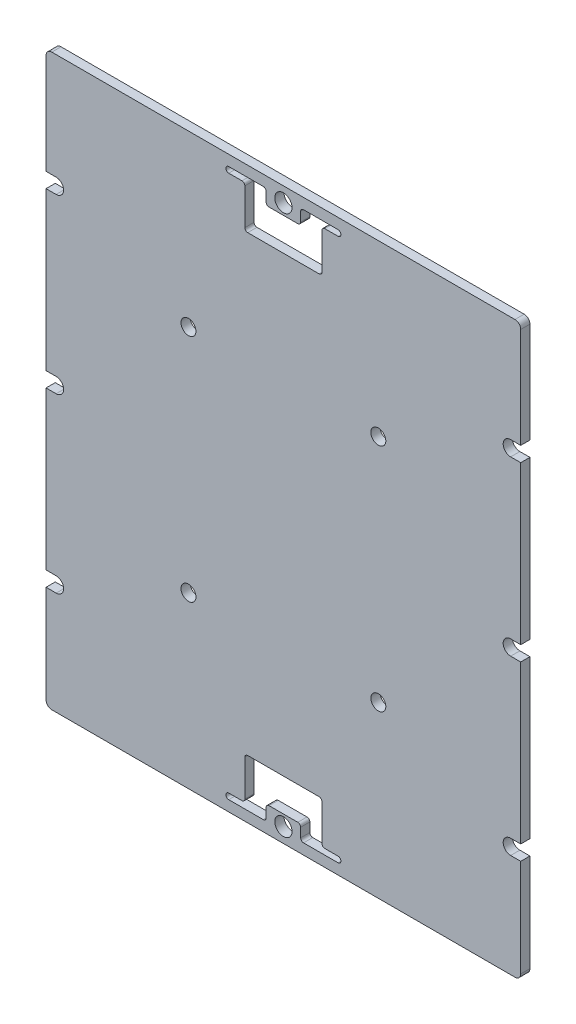
SolidWorks part; units mm, degrees
material "FR4_stuffedProtoboard"
ref_plane "Front Plane" through (0, 0, 0) normal (0, 0, 1) x (1, 0, 0)
ref_plane "Top Plane" through (0, 0, 0) normal (0, 1, 0) x (1, 0, 0)
ref_plane "Right Plane" through (0, 0, 0) normal (1, 0, 0) x (0, 0, -1)
sketch "Sketch2" plane through (0, 0, 0) normal (0, 0, 1) x (1, 0, 0)
  line L0 (39.5, 49.75) -> (-39.5, 49.75) construction
  line L1 (-41.5, 49.75) -> (41.5, 49.75) construction
  line L2 (-41.5, 49.75) -> (-41.5, -49.75) construction
  line L3 (-41.5, -49.75) -> (41.5, -49.75) construction
  line L4 (41.5, 49.75) -> (41.5, -49.75) construction
  line L5 (-41.5, 49.75) -> (41.5, -49.75) construction
  line L6 (-41.5, -49.75) -> (41.5, 49.75) construction
  line L7 (41.5, 51.75) -> (41.5, 40.35) construction
  line L8 (-41.5, 49.75) -> (41.5, 49.75) construction
  line L9 (41.5, 49.75) -> (41.5, -49.75) construction
  line L10 (-41.5, -49.75) -> (41.5, -49.75) construction
  line L11 (-41.5, 49.75) -> (-41.5, -49.75) construction
  line L12 (-37, -31.85) -> (37, -31.85) construction
  line L13 (-37, -30.25) -> (37, -30.25) construction
  line L14 (-37, -21.85) -> (37, -21.85) construction
  line L15 (-37, -20.25) -> (37, -20.25) construction
  line L16 (-37, -11.85) -> (37, -11.85) construction
  line L17 (-37, -10.25) -> (37, -10.25) construction
  line L18 (-37, -1.85) -> (37, -1.85) construction
  line L19 (-37, -0.25) -> (37, -0.25) construction
  line L20 (-37, 8.15) -> (37, 8.15) construction
  line L21 (-37, 9.75) -> (37, 9.75) construction
  line L22 (-37, 18.15) -> (37, 18.15) construction
  line L23 (-37, 19.75) -> (37, 19.75) construction
  line L24 (-37, 28.15) -> (37, 28.15) construction
  line L25 (-37, 29.75) -> (37, 29.75) construction
  line L26 (-37, 38.15) -> (37, 38.15) construction
  line L27 (-37, 39.75) -> (37, 39.75) construction
  line L28 (-37, -31.85) -> (37, -31.85) construction
  line L29 (-37, -30.25) -> (37, -30.25) construction
  line L30 (-37, -21.85) -> (37, -21.85) construction
  line L31 (-37, -20.25) -> (37, -20.25) construction
  line L32 (-37, -11.85) -> (37, -11.85) construction
  line L33 (-37, -10.25) -> (37, -10.25) construction
  line L34 (-37, -1.85) -> (37, -1.85) construction
  line L35 (-37, -0.25) -> (37, -0.25) construction
  line L36 (-37, 8.15) -> (37, 8.15) construction
  line L37 (-37, 9.75) -> (37, 9.75) construction
  line L38 (-37, 18.15) -> (37, 18.15) construction
  line L39 (-37, 19.75) -> (37, 19.75) construction
  line L40 (-37, 28.15) -> (37, 28.15) construction
  line L41 (-37, 29.75) -> (37, 29.75) construction
  line L42 (-37, 38.15) -> (37, 38.15) construction
  line L43 (-37, 39.75) -> (37, 39.75) construction
  line L44 (-37, -40.25) -> (37, -40.25) construction
  line L45 (-37, -41.85) -> (37, -41.85) construction
  line L46 (-41.5, 51.75) -> (-41.5, 40.35) construction
  line L47 (39.5, -49.75) -> (-39.5, -49.75) construction
  line L48 (41.5, -31.9) -> (41.5, -51.75) construction
  line L49 (-41.25, 49.5) -> (41.25, 49.5)
  line L50 (41.25, 49.5) -> (41.25, -49.5)
  line L51 (-41.25, -49.5) -> (41.25, -49.5)
  line L52 (-41.25, 49.5) -> (-41.25, -49.5)
  circle A0 centre (0, 46.95) radius 1.5 construction
  circle A1 centre (0, 46.95) radius 0.8 construction
  circle A2 centre (0, 46.95) radius 1.5 construction
  circle A3 centre (0, 46.95) radius 0.8
  circle A4 centre (-39.5, -30.25) radius 0.8 construction
  circle A5 centre (-39.5, -0.25) radius 0.8 construction
  circle A6 centre (-39.5, 29.75) radius 0.8 construction
  circle A7 centre (-39.5, -30.25) radius 0.8
  circle A8 centre (-39.5, -0.25) radius 0.8
  circle A9 centre (-39.5, 29.75) radius 0.8
  circle A10 centre (39.5, -30.25) radius 0.8 construction
  circle A11 centre (39.5, -0.25) radius 0.8 construction
  circle A12 centre (39.5, 29.75) radius 0.8 construction
  circle A13 centre (39.5, -30.25) radius 0.8
  circle A14 centre (39.5, -0.25) radius 0.8
  circle A15 centre (39.5, 29.75) radius 0.8
  circle A16 centre (0, -46.95) radius 0.8 construction
  circle A17 centre (0, -46.95) radius 0.8
  circle A18 centre (0, -46.95) radius 1.5 construction
  circle A19 centre (0, -46.95) radius 1.5
  circle A20 centre (-16.5, 20) radius 1.75 construction
  circle A21 centre (-16.5, 20) radius 0.8 construction
  circle A22 centre (-16.5, 20) radius 1.75 construction
  circle A23 centre (-16.5, 20) radius 0.8
  circle A24 centre (16.5, 20) radius 1.75 construction
  circle A25 centre (16.5, 20) radius 0.8 construction
  circle A26 centre (16.5, 20) radius 1.75 construction
  circle A27 centre (16.5, 20) radius 0.8
  circle A28 centre (16.5, -20) radius 1.75 construction
  circle A29 centre (-16.5, -20) radius 1.75 construction
  circle A30 centre (16.5, -20) radius 1.75 construction
  circle A31 centre (-16.5, -20) radius 1.75 construction
  circle A32 centre (-16.5, -20) radius 0.8 construction
  circle A33 centre (-16.5, -20) radius 0.8
  circle A34 centre (16.5, -20) radius 0.8 construction
  circle A35 centre (16.5, -20) radius 0.8
  point P0 (0, 0)
  point P74 (0, -40.25)
  point P75 (0, -31.85)
  point P76 (0, -41.85)
  dimension "D2" = 10
  dimension "D3" = 1.6
  dimension "D1" = 0.25
extrude "pcb extrude" add sketch "Sketch2" along normal mid plane 1.6 contours L4 L1 L2 L3 A2 | A2 A3 | L2 L1 L4 L3 region at (0, 0.0296, 0)
sketch "connector locations" plane through (0, 0, 0.8) normal (0, 0, 1) x (1, 0, 0)
  line L0 (34.5, 45.75) -> (4.5, 45.75) construction
  line L1 (-2.5, 44.75) -> (2.5, 44.75) construction
  line L2 (-4.5, 45.75) -> (-34.5, 45.75) construction
  line L3 (34.5, 45.75) -> (4.5, 45.75)
  line L4 (-2.5, 44.75) -> (2.5, 44.75)
  line L5 (-4.5, 45.75) -> (-34.5, 45.75)
  line L6 (-37, 43.25) -> (-37, -43.25) construction
  line L7 (-37, 43.25) -> (-37, -43.25)
  line L8 (37, -43.25) -> (37, 43.25) construction
  line L9 (37, -43.25) -> (37, 43.25)
  line L10 (4.5, -45.75) -> (34.5, -45.75) construction
  line L11 (4.5, -45.75) -> (34.5, -45.75)
  line L12 (-34.5, -45.75) -> (-4.5, -45.75) construction
  line L13 (-2.5, -44.75) -> (2.5, -44.75) construction
  line L14 (-34.5, -45.75) -> (-4.5, -45.75)
  line L15 (-2.5, -44.75) -> (2.5, -44.75)
  line L16 (-37, 39.75) -> (37, 39.75) construction
  line L17 (-33.9182, 41.909) -> (-9.2802, 41.909)
  line L18 (-33.9182, 41.909) -> (-33.9182, 43.306)
  line L19 (-33.9182, 43.306) -> (-9.2802, 43.306)
  line L20 (-9.2802, 41.909) -> (-9.2802, 43.306)
  line L21 (-33.9182, 41.909) -> (-9.2802, 43.306) construction
  line L22 (-33.9182, 43.306) -> (-9.2802, 41.909) construction
  line L23 (-33.9182, 33.306) -> (-22.0818, 33.306)
  line L24 (-33.9182, 33.306) -> (-33.9182, 31.909)
  line L25 (-33.9182, 31.909) -> (-22.0818, 31.909)
  line L26 (-22.0818, 33.306) -> (-22.0818, 31.909)
  line L27 (-33.9182, 33.306) -> (-22.0818, 31.909) construction
  line L28 (-33.9182, 31.909) -> (-22.0818, 33.306) construction
  line L29 (-12.319, 33.306) -> (12.319, 33.306)
  line L30 (-12.319, 33.306) -> (-12.319, 31.909)
  line L31 (-12.319, 31.909) -> (12.319, 31.909)
  line L32 (12.319, 33.306) -> (12.319, 31.909)
  line L33 (-12.319, 33.306) -> (12.319, 31.909) construction
  line L34 (-12.319, 31.909) -> (12.319, 33.306) construction
  line L35 (-33.9182, 23.306) -> (-22.0818, 23.306)
  line L36 (-33.9182, 23.306) -> (-33.9182, 21.909)
  line L37 (-33.9182, 21.909) -> (-22.0818, 21.909)
  line L38 (-33.9182, 23.306) -> (-22.0818, 21.909) construction
  line L39 (-33.9182, 21.909) -> (-22.0818, 23.306) construction
  line L40 (-22.0818, 23.306) -> (-22.0818, 21.909)
  line L41 (-12.319, 23.306) -> (-12.319, 21.909)
  line L42 (-12.319, 23.306) -> (12.319, 23.306)
  line L43 (-12.319, 21.909) -> (12.319, 21.909)
  line L44 (-12.319, 23.306) -> (12.319, 21.909) construction
  line L45 (-12.319, 21.909) -> (12.319, 23.306) construction
  line L46 (12.319, 23.306) -> (12.319, 21.909)
  line L47 (-33.9182, 13.306) -> (-22.0818, 13.306)
  line L48 (-33.9182, 13.306) -> (-33.9182, 11.909)
  line L49 (-33.9182, 11.909) -> (-22.0818, 11.909)
  line L50 (-33.9182, 13.306) -> (-22.0818, 11.909) construction
  line L51 (-33.9182, 11.909) -> (-22.0818, 13.306) construction
  line L52 (-22.0818, 13.306) -> (-22.0818, 11.909)
  line L53 (-12.319, 13.306) -> (-12.319, 11.909)
  line L54 (-12.319, 13.306) -> (12.319, 13.306)
  line L55 (-12.319, 11.909) -> (12.319, 11.909)
  line L56 (-12.319, 13.306) -> (12.319, 11.909) construction
  line L57 (-12.319, 11.909) -> (12.319, 13.306) construction
  line L58 (12.319, 13.306) -> (12.319, 11.909)
  line L59 (-33.9182, 3.306) -> (-22.0818, 3.306)
  line L60 (-33.9182, 3.306) -> (-33.9182, 1.909)
  line L61 (-33.9182, 1.909) -> (-22.0818, 1.909)
  line L62 (-33.9182, 3.306) -> (-22.0818, 1.909) construction
  line L63 (-33.9182, 1.909) -> (-22.0818, 3.306) construction
  line L64 (-22.0818, 3.306) -> (-22.0818, 1.909)
  line L65 (-12.319, 3.306) -> (-12.319, 1.909)
  line L66 (-12.319, 3.306) -> (12.319, 3.306)
  line L67 (-12.319, 1.909) -> (12.319, 1.909)
  line L68 (-12.319, 3.306) -> (12.319, 1.909) construction
  line L69 (-12.319, 1.909) -> (12.319, 3.306) construction
  line L70 (12.319, 3.306) -> (12.319, 1.909)
  line L71 (-33.9182, -6.694) -> (-22.0818, -6.694)
  line L72 (-33.9182, -6.694) -> (-33.9182, -8.091)
  line L73 (-33.9182, -8.091) -> (-22.0818, -8.091)
  line L74 (-33.9182, -6.694) -> (-22.0818, -8.091) construction
  line L75 (-33.9182, -8.091) -> (-22.0818, -6.694) construction
  line L76 (-22.0818, -6.694) -> (-22.0818, -8.091)
  line L77 (-12.319, -6.694) -> (-12.319, -8.091)
  line L78 (-12.319, -6.694) -> (12.319, -6.694)
  line L79 (-12.319, -8.091) -> (12.319, -8.091)
  line L80 (-12.319, -6.694) -> (12.319, -8.091) construction
  line L81 (-12.319, -8.091) -> (12.319, -6.694) construction
  line L82 (12.319, -6.694) -> (12.319, -8.091)
  line L83 (-33.9182, -16.694) -> (-22.0818, -16.694)
  line L84 (-33.9182, -16.694) -> (-33.9182, -18.091)
  line L85 (-33.9182, -18.091) -> (-22.0818, -18.091)
  line L86 (-33.9182, -16.694) -> (-22.0818, -18.091) construction
  line L87 (-33.9182, -18.091) -> (-22.0818, -16.694) construction
  line L88 (-22.0818, -16.694) -> (-22.0818, -18.091)
  line L89 (-12.319, -16.694) -> (-12.319, -18.091)
  line L90 (-12.319, -16.694) -> (12.319, -16.694)
  line L91 (-12.319, -18.091) -> (12.319, -18.091)
  line L92 (-12.319, -16.694) -> (12.319, -18.091) construction
  line L93 (-12.319, -18.091) -> (12.319, -16.694) construction
  line L94 (12.319, -16.694) -> (12.319, -18.091)
  line L95 (-33.9182, -26.694) -> (-22.0818, -26.694)
  line L96 (-33.9182, -26.694) -> (-33.9182, -28.091)
  line L97 (-33.9182, -28.091) -> (-22.0818, -28.091)
  line L98 (-33.9182, -26.694) -> (-22.0818, -28.091) construction
  line L99 (-33.9182, -28.091) -> (-22.0818, -26.694) construction
  line L100 (-22.0818, -26.694) -> (-22.0818, -28.091)
  line L101 (-12.319, -26.694) -> (-12.319, -28.091)
  line L102 (-12.319, -26.694) -> (12.319, -26.694)
  line L103 (-12.319, -28.091) -> (12.319, -28.091)
  line L104 (-12.319, -26.694) -> (12.319, -28.091) construction
  line L105 (-12.319, -28.091) -> (12.319, -26.694) construction
  line L106 (12.319, -26.694) -> (12.319, -28.091)
  line L111 (-35.52, -38.1) -> (-10.98, -38.1)
  line L116 (-35.52, -38.1) -> (-35.52, -37.9)
  line L117 (-35.52, -37.9) -> (-10.98, -37.9)
  line L119 (0, 32.6075) -> (0, 22.6075) construction
  line L120 (-37, 29.75) -> (37, 29.75) construction
  line L121 (32.92, 41.02) -> (35.08, 38.84) construction
  line L122 (32.92, 38.84) -> (35.08, 41.02) construction
  line L123 (26.92, 38.84) -> (29.08, 41.02) construction
  line L124 (26.92, 41.02) -> (29.08, 38.84) construction
  line L125 (20.92, 38.84) -> (23.08, 41.02) construction
  line L126 (20.92, 41.02) -> (23.08, 38.84) construction
  line L127 (26.92, 28.84) -> (29.08, 31.02) construction
  line L128 (26.92, 31.02) -> (29.08, 28.84) construction
  line L129 (20.92, 28.84) -> (23.08, 31.02) construction
  line L130 (20.92, 31.02) -> (23.08, 28.84) construction
  line L131 (26.92, 18.84) -> (29.08, 21.02) construction
  line L132 (26.92, 21.02) -> (29.08, 18.84) construction
  line L133 (20.92, 18.84) -> (23.08, 21.02) construction
  line L134 (20.92, 21.02) -> (23.08, 18.84) construction
  line L135 (26.92, 8.84) -> (29.08, 11.02) construction
  line L136 (26.92, 11.02) -> (29.08, 8.84) construction
  line L137 (20.92, 8.84) -> (23.08, 11.02) construction
  line L138 (20.92, 11.02) -> (23.08, 8.84) construction
  line L139 (26.92, -1.16) -> (29.08, 1.02) construction
  line L140 (26.92, 1.02) -> (29.08, -1.16) construction
  line L141 (20.92, -1.16) -> (23.08, 1.02) construction
  line L142 (20.92, 1.02) -> (23.08, -1.16) construction
  line L143 (26.92, -11.16) -> (29.08, -8.98) construction
  line L144 (26.92, -8.98) -> (29.08, -11.16) construction
  line L145 (20.92, -11.16) -> (23.08, -8.98) construction
  line L146 (20.92, -8.98) -> (23.08, -11.16) construction
  line L147 (26.92, -21.16) -> (29.08, -18.98) construction
  line L148 (26.92, -18.98) -> (29.08, -21.16) construction
  line L149 (20.92, -21.16) -> (23.08, -18.98) construction
  line L150 (20.92, -18.98) -> (23.08, -21.16) construction
  line L151 (26.92, -31.16) -> (29.08, -28.98) construction
  line L152 (26.92, -28.98) -> (29.08, -31.16) construction
  line L153 (20.92, -31.16) -> (23.08, -28.98) construction
  line L154 (20.92, -28.98) -> (23.08, -31.16) construction
  line L155 (26.92, -41.16) -> (29.08, -38.98) construction
  line L156 (26.92, -38.98) -> (29.08, -41.16) construction
  line L157 (20.92, -41.16) -> (23.08, -38.98) construction
  line L158 (20.92, -38.98) -> (23.08, -41.16) construction
  line L159 (32.92, 28.84) -> (35.08, 31.02) construction
  line L160 (32.92, 31.02) -> (35.08, 28.84) construction
  line L161 (32.92, 18.84) -> (35.08, 21.02) construction
  line L162 (32.92, 21.02) -> (35.08, 18.84) construction
  line L163 (32.92, 8.84) -> (35.08, 11.02) construction
  line L164 (32.92, 11.02) -> (35.08, 8.84) construction
  line L165 (32.92, -1.16) -> (35.08, 1.02) construction
  line L166 (32.92, 1.02) -> (35.08, -1.16) construction
  line L167 (32.92, -11.16) -> (35.08, -8.98) construction
  line L168 (32.92, -8.98) -> (35.08, -11.16) construction
  line L169 (32.92, -21.16) -> (35.08, -18.98) construction
  line L170 (32.92, -18.98) -> (35.08, -21.16) construction
  line L171 (32.92, -31.16) -> (35.08, -28.98) construction
  line L172 (32.92, -28.98) -> (35.08, -31.16) construction
  line L173 (32.92, -41.16) -> (35.08, -38.98) construction
  line L174 (32.92, -38.98) -> (35.08, -41.16) construction
  line L175 (34, 39.93) -> (28, 39.93) construction
  line L176 (34, 39.93) -> (34, 29.93) construction
  line L177 (-36.51, -37.5) -> (-36.51, -46.51)
  line L178 (-36.51, -46.51) -> (-9.99, -46.51)
  line L179 (-9.99, -46.51) -> (-9.99, -37.5)
  line L180 (-41.25, -49.5) -> (41.25, -49.5) construction
  line L181 (-41.25, 49.5) -> (-41.25, -49.5) construction
  line L182 (-10.98, -38.1) -> (-10.98, -37.9)
  line L183 (-35.52, -38.1) -> (-10.98, -37.9) construction
  line L184 (-35.52, -37.9) -> (-10.98, -38.1) construction
  arc A0 (4.5, 45.75) -> (2.5, 44.75) centre (4.5, 43.25) ccw construction
  arc A1 (-2.5, 44.75) -> (-4.5, 45.75) centre (-4.5, 43.25) ccw construction
  arc A2 (-34.5, 45.75) -> (-37, 43.25) centre (-34.5, 43.25) ccw construction
  arc A3 (4.5, 45.75) -> (2.5, 44.75) centre (4.5, 43.25) ccw
  arc A4 (-2.5, 44.75) -> (-4.5, 45.75) centre (-4.5, 43.25) ccw
  arc A5 (-34.5, 45.75) -> (-37, 43.25) centre (-34.5, 43.25) ccw
  arc A6 (37, 43.25) -> (34.5, 45.75) centre (34.5, 43.25) ccw construction
  arc A7 (37, 43.25) -> (34.5, 45.75) centre (34.5, 43.25) ccw
  arc A8 (34.5, -45.75) -> (37, -43.25) centre (34.5, -43.25) ccw construction
  arc A9 (34.5, -45.75) -> (37, -43.25) centre (34.5, -43.25) ccw
  arc A10 (-37, -43.25) -> (-34.5, -45.75) centre (-34.5, -43.25) ccw construction
  arc A11 (-4.5, -45.75) -> (-2.5, -44.75) centre (-4.5, -43.25) ccw construction
  arc A12 (2.5, -44.75) -> (4.5, -45.75) centre (4.5, -43.25) ccw construction
  arc A13 (-37, -43.25) -> (-34.5, -45.75) centre (-34.5, -43.25) ccw
  arc A14 (-4.5, -45.75) -> (-2.5, -44.75) centre (-4.5, -43.25) ccw
  arc A15 (2.5, -44.75) -> (4.5, -45.75) centre (4.5, -43.25) ccw
  circle A16 centre (-21.5992, 42.6075) radius 0.5
  circle A17 centre (0, 32.6075) radius 0.5
  circle A18 centre (-28, 32.6075) radius 0.5
  circle A19 centre (-28, 22.6075) radius 0.5
  circle A20 centre (0, 22.6075) radius 0.5
  circle A21 centre (-28, 12.6075) radius 0.5
  circle A22 centre (0, 12.6075) radius 0.5
  circle A23 centre (-28, 2.6075) radius 0.5
  circle A24 centre (0, 2.6075) radius 0.5
  circle A25 centre (-28, -7.3925) radius 0.5
  circle A26 centre (0, -7.3925) radius 0.5
  circle A27 centre (-28, -17.3925) radius 0.5
  circle A28 centre (0, -17.3925) radius 0.5
  circle A29 centre (-28, -27.3925) radius 0.5
  circle A30 centre (0, -27.3925) radius 0.5
  circle A33 centre (35.08, 41.02) radius 0.32
  circle A34 centre (32.92, 38.84) radius 0.32
  circle A35 centre (35.08, 38.84) radius 0.32
  circle A36 centre (32.92, 41.02) radius 0.32
  circle A37 centre (26.92, 41.02) radius 0.32
  circle A38 centre (29.08, 41.02) radius 0.32
  circle A39 centre (26.92, 38.84) radius 0.32
  circle A40 centre (29.08, 38.84) radius 0.32
  circle A41 centre (20.92, 41.02) radius 0.32
  circle A42 centre (23.08, 41.02) radius 0.32
  circle A43 centre (20.92, 38.84) radius 0.32
  circle A44 centre (23.08, 38.84) radius 0.32
  circle A45 centre (26.92, 31.02) radius 0.32
  circle A46 centre (29.08, 31.02) radius 0.32
  circle A47 centre (26.92, 28.84) radius 0.32
  circle A48 centre (29.08, 28.84) radius 0.32
  circle A49 centre (20.92, 31.02) radius 0.32
  circle A50 centre (23.08, 31.02) radius 0.32
  circle A51 centre (20.92, 28.84) radius 0.32
  circle A52 centre (23.08, 28.84) radius 0.32
  circle A53 centre (26.92, 21.02) radius 0.32
  circle A54 centre (29.08, 21.02) radius 0.32
  circle A55 centre (26.92, 18.84) radius 0.32
  circle A56 centre (29.08, 18.84) radius 0.32
  circle A57 centre (20.92, 21.02) radius 0.32
  circle A58 centre (23.08, 21.02) radius 0.32
  circle A59 centre (20.92, 18.84) radius 0.32
  circle A60 centre (23.08, 18.84) radius 0.32
  circle A61 centre (26.92, 11.02) radius 0.32
  circle A62 centre (29.08, 11.02) radius 0.32
  circle A63 centre (26.92, 8.84) radius 0.32
  circle A64 centre (29.08, 8.84) radius 0.32
  circle A65 centre (20.92, 11.02) radius 0.32
  circle A66 centre (23.08, 11.02) radius 0.32
  circle A67 centre (20.92, 8.84) radius 0.32
  circle A68 centre (23.08, 8.84) radius 0.32
  circle A69 centre (26.92, 1.02) radius 0.32
  circle A70 centre (29.08, 1.02) radius 0.32
  circle A71 centre (26.92, -1.16) radius 0.32
  circle A72 centre (29.08, -1.16) radius 0.32
  circle A73 centre (20.92, 1.02) radius 0.32
  circle A74 centre (23.08, 1.02) radius 0.32
  circle A75 centre (20.92, -1.16) radius 0.32
  circle A76 centre (23.08, -1.16) radius 0.32
  circle A77 centre (26.92, -8.98) radius 0.32
  circle A78 centre (29.08, -8.98) radius 0.32
  circle A79 centre (26.92, -11.16) radius 0.32
  circle A80 centre (29.08, -11.16) radius 0.32
  circle A81 centre (20.92, -8.98) radius 0.32
  circle A82 centre (23.08, -8.98) radius 0.32
  circle A83 centre (20.92, -11.16) radius 0.32
  circle A84 centre (23.08, -11.16) radius 0.32
  circle A85 centre (26.92, -18.98) radius 0.32
  circle A86 centre (29.08, -18.98) radius 0.32
  circle A87 centre (26.92, -21.16) radius 0.32
  circle A88 centre (29.08, -21.16) radius 0.32
  circle A89 centre (20.92, -18.98) radius 0.32
  circle A90 centre (23.08, -18.98) radius 0.32
  circle A91 centre (20.92, -21.16) radius 0.32
  circle A92 centre (23.08, -21.16) radius 0.32
  circle A93 centre (26.92, -28.98) radius 0.32
  circle A94 centre (29.08, -28.98) radius 0.32
  circle A95 centre (26.92, -31.16) radius 0.32
  circle A96 centre (29.08, -31.16) radius 0.32
  circle A97 centre (20.92, -28.98) radius 0.32
  circle A98 centre (23.08, -28.98) radius 0.32
  circle A99 centre (20.92, -31.16) radius 0.32
  circle A100 centre (23.08, -31.16) radius 0.32
  circle A101 centre (26.92, -38.98) radius 0.32
  circle A102 centre (29.08, -38.98) radius 0.32
  circle A103 centre (26.92, -41.16) radius 0.32
  circle A104 centre (29.08, -41.16) radius 0.32
  circle A105 centre (20.92, -38.98) radius 0.32
  circle A106 centre (23.08, -38.98) radius 0.32
  circle A107 centre (20.92, -41.16) radius 0.32
  circle A108 centre (23.08, -41.16) radius 0.32
  circle A109 centre (32.92, 31.02) radius 0.32
  circle A110 centre (35.08, 31.02) radius 0.32
  circle A111 centre (32.92, 28.84) radius 0.32
  circle A112 centre (35.08, 28.84) radius 0.32
  circle A113 centre (32.92, 21.02) radius 0.32
  circle A114 centre (35.08, 21.02) radius 0.32
  circle A115 centre (32.92, 18.84) radius 0.32
  circle A116 centre (35.08, 18.84) radius 0.32
  circle A117 centre (32.92, 11.02) radius 0.32
  circle A118 centre (35.08, 11.02) radius 0.32
  circle A119 centre (32.92, 8.84) radius 0.32
  circle A120 centre (35.08, 8.84) radius 0.32
  circle A121 centre (32.92, 1.02) radius 0.32
  circle A122 centre (35.08, 1.02) radius 0.32
  circle A123 centre (32.92, -1.16) radius 0.32
  circle A124 centre (35.08, -1.16) radius 0.32
  circle A125 centre (32.92, -8.98) radius 0.32
  circle A126 centre (35.08, -8.98) radius 0.32
  circle A127 centre (32.92, -11.16) radius 0.32
  circle A128 centre (35.08, -11.16) radius 0.32
  circle A129 centre (32.92, -18.98) radius 0.32
  circle A130 centre (35.08, -18.98) radius 0.32
  circle A131 centre (32.92, -21.16) radius 0.32
  circle A132 centre (35.08, -21.16) radius 0.32
  circle A133 centre (32.92, -28.98) radius 0.32
  circle A134 centre (35.08, -28.98) radius 0.32
  circle A135 centre (32.92, -31.16) radius 0.32
  circle A136 centre (35.08, -31.16) radius 0.32
  circle A137 centre (32.92, -38.98) radius 0.32
  circle A138 centre (35.08, -38.98) radius 0.32
  circle A139 centre (32.92, -41.16) radius 0.32
  circle A140 centre (35.08, -41.16) radius 0.32
  point P18 (-21.5992, 42.6075)
  point P29 (-28, 32.6075)
  point P34 (0, 32.6075)
  point P50 (-28, 22.6075)
  point P55 (0, 22.6075)
  point P64 (-28, 12.6075)
  point P69 (0, 12.6075)
  point P78 (-28, 2.6075)
  point P83 (0, 2.6075)
  point P92 (-28, -7.3925)
  point P97 (0, -7.3925)
  point P106 (-28, -17.3925)
  point P111 (0, -17.3925)
  point P120 (-28, -27.3925)
  point P125 (0, -27.3925)
  point P134 (-23.25, -38)
  point P135 (-23.25, -46.51)
  point P136 (-23.25, -38)
  point P165 (34, 39.93)
  point P170 (28, 39.93)
  point P179 (22, 39.93)
  point P188 (28, 29.93)
  point P197 (22, 29.93)
  point P206 (28, 19.93)
  point P215 (22, 19.93)
  point P224 (28, 9.93)
  point P233 (22, 9.93)
  point P242 (28, -0.07)
  point P251 (22, -0.07)
  point P260 (28, -10.07)
  point P269 (22, -10.07)
  point P278 (28, -20.07)
  point P287 (22, -20.07)
  point P296 (28, -30.07)
  point P305 (22, -30.07)
  point P314 (28, -40.07)
  point P323 (22, -40.07)
  point P332 (34, 29.93)
  point P341 (34, 19.93)
  point P350 (34, 9.93)
  point P359 (34, -0.07)
  point P368 (34, -10.07)
  point P377 (34, -20.07)
  point P386 (34, -30.07)
  point P395 (34, -40.07)
  dimension "D4" = 1
  dimension "D5" = 11.8364
  dimension "D10" = 0.64
  dimension "D1" = 24.638
  dimension "D2" = 1.397
  dimension "D3" = 2.159
  dimension "D6" = 28
  dimension "D8" = 10
  dimension "D9" = 2.159
  dimension "D11" = 2.18
  dimension "D12" = 2.16
  dimension "D13" = 0.18
  dimension "D14" = 34
  dimension "D17" = 6
  dimension "D18" = 10
  dimension "D19" = 2.99
  dimension "D20" = 4.74
  dimension "D21" = 26.52
  dimension "D22" = 9.01
  dimension "D23" = 8.51
  dimension "D24" = 24.54
  dimension "D25" = 0.2
  dimension "D7" = 7
  dimension "D15" = 3
  dimension "D16" = 9
fillet "corner fillets" radius 1 4 edges at (41.25, -49.5, 0) (-41.25, -49.5, 0) (41.25, 49.5, 0) (-41.25, 49.5, 0)
sketch "Sketch4" plane through (0, 0, 0.8) normal (0, 0, 1) x (1, 0, 0)
  line L0 (0, 46.95) -> (0, 39.35) construction
  line L1 (6.7, 39.35) -> (-6.7, 39.35)
  line L2 (-6.7, 39.35) -> (-6.7, 46.65)
  line L3 (-6.7, 46.65) -> (-9.5, 46.65)
  line L4 (-4.5, 45.75) -> (-34.5, 45.75) construction
  line L5 (-9.5, 47.65) -> (-3, 47.65)
  line L6 (-3, 47.65) -> (-3, 45.05)
  line L7 (-3, 45.05) -> (3, 45.05)
  line L8 (3, 47.65) -> (3, 45.05)
  line L9 (6.7, 39.35) -> (6.7, 46.65)
  line L10 (6.7, 46.65) -> (9.5, 46.65)
  line L11 (9.5, 47.65) -> (3, 47.65)
  line L12 (0.88, 0) -> (-0.88, 0) construction
  line L13 (6.7, -46.65) -> (9.5, -46.65)
  line L14 (9.5, -47.65) -> (3, -47.65)
  line L15 (3, -47.65) -> (3, -45.05)
  line L16 (-3, -45.05) -> (3, -45.05)
  line L17 (-3, -47.65) -> (-3, -45.05)
  line L18 (-9.5, -47.65) -> (-3, -47.65)
  line L19 (-6.7, -46.65) -> (-9.5, -46.65)
  line L20 (-6.7, -39.35) -> (-6.7, -46.65)
  line L21 (6.7, -39.35) -> (-6.7, -39.35)
  line L22 (6.7, -39.35) -> (6.7, -46.65)
  arc A0 (-9.5, 47.65) -> (-9.5, 46.65) centre (-9.5, 47.15) ccw
  arc A1 (9.5, 47.65) -> (9.5, 46.65) centre (9.5, 47.15) cw
  circle A2 centre (0, 46.95) radius 1.5
  arc A3 (9.5, -47.65) -> (9.5, -46.65) centre (9.5, -47.15) ccw
  arc A4 (-9.5, -47.65) -> (-9.5, -46.65) centre (-9.5, -47.15) cw
  point P17 (0, 45.05)
  dimension "D3" = 1
  dimension "D8" = 3
  dimension "D1" = 3
  dimension "D2" = 9.5
  dimension "D4" = 0.9
  dimension "D5" = 7.3
  dimension "D6" = 2.6
  dimension "D7" = 3.7
extrude "solar holes" cut sketch "Sketch4" against normal through all
fillet "solar hole fillets" radius 0.5 16 edges at (6.7, 46.65, 0) (3, 47.65, 0) (3, 45.05, 0) (6.7, 39.35, 0) (-6.7, 39.35, 0) (-6.7, 46.65, 0) (-3, 45.05, 0) (-3, 47.65, 0) (3, -47.65, 0) (3, -45.05, 0) (-3, -47.65, 0) (-3, -45.05, 0) (-6.7, -46.65, 0) (6.7, -46.65, 0) (6.7, -39.35, 0) (-6.7, -39.35, 0)
sketch "m2 locations" plane through (0, 0, 0.8) normal (0, 0, 1) x (1, 0, 0)
  point P0 (-39.5, 29.75)
  point P1 (-39.5, -0.25)
  point P3 (-39.5, -30.25)
  point P5 (-16.5, -20)
  point P7 (-16.5, 20)
  point P9 (16.5, 20)
  point P11 (16.5, -20)
  point P13 (39.5, -30.25)
  point P15 (39.5, -0.25)
  point P17 (39.5, 29.75)
hole_wizard "M2 Clearance Holes" positions "Sketch8" profile "Sketch9" hole size "M2" standard "ANSI Metric" end condition through all
sketch "Sketch8" plane through (0, 0, 0.8) normal (0, 0, 1) x (1, 0, 0)
  point P0 (-39.5, 29.75)
  point P3 (-39.5, -0.25)
  point P6 (-16.5, 20)
  point P9 (16.5, 20)
  point P12 (16.5, -20)
  point P15 (-16.5, -20)
  point P18 (39.5, 29.75)
  point P21 (39.5, -0.25)
  point P24 (39.5, -30.25)
  point P27 (-39.5, -30.25)
sketch "Sketch9" plane through (-39.5, 29.75, 0.8) normal (1, 0, 0) x (0, -1, 0)
  line L0 (0, 0) -> (0, 1.6)
  line L1 (0, 1.6) -> (1.3, 1.6)
  line L2 (1.3, 1.6) -> (1.3, 0)
  line L5 (1.3, 0) -> (0, 0)
  line L11 (0, -6.35) -> (0, 107.95) construction
  dimension "Thru Hole Dia." = 2.6
  dimension "Thru Hole Depth" = 1.6
sketch "Sketch10" plane through (0, 0, 0.8) normal (0, 0, 1) x (1, 0, 0)
  line L0 (-41.25, 48.5) -> (-41.25, -48.5) construction
  line L1 (-39.5, 31.05) -> (-41.25, 31.05)
  line L2 (-39.5, 31.05) -> (-39.5, 28.45)
  line L3 (-39.5, 28.45) -> (-41.25, 28.45)
  line L4 (-41.25, 31.05) -> (-41.25, 28.45)
  line L5 (41.25, 48.5) -> (41.25, -48.5) construction
  line L6 (-39.5, 1.05) -> (-41.25, 1.05)
  line L7 (-39.5, 1.05) -> (-39.5, -1.55)
  line L8 (-39.5, -1.55) -> (-41.25, -1.55)
  line L9 (-41.25, 1.05) -> (-41.25, -1.55)
  line L10 (-39.5, -28.95) -> (-41.25, -28.95)
  line L11 (-39.5, -28.95) -> (-39.5, -31.55)
  line L12 (-39.5, -31.55) -> (-41.25, -31.55)
  line L13 (-41.25, -28.95) -> (-41.25, -31.55)
  line L14 (39.5, -28.95) -> (41.25, -28.95)
  line L15 (39.5, -28.95) -> (39.5, -31.55)
  line L16 (39.5, -31.55) -> (41.25, -31.55)
  line L17 (41.25, -28.95) -> (41.25, -31.55)
  line L19 (39.5, 1.05) -> (41.25, 1.05)
  line L20 (39.5, 1.05) -> (39.5, -1.55)
  line L21 (39.5, -1.55) -> (41.25, -1.55)
  line L22 (41.25, 1.05) -> (41.25, -1.55)
  line L23 (39.5, 31.05) -> (41.25, 31.05)
  line L24 (39.5, 31.05) -> (39.5, 28.45)
  line L25 (39.5, 28.45) -> (41.25, 28.45)
  line L26 (41.25, 31.05) -> (41.25, 28.45)
  circle A0 centre (-39.5, 29.75) radius 1.3 construction
  circle A1 centre (-39.5, -0.25) radius 1.3 construction
  circle A2 centre (-39.5, -30.25) radius 1.3 construction
  circle A3 centre (39.5, -30.25) radius 1.3 construction
  circle A4 centre (39.5, -0.25) radius 1.3 construction
  circle A5 centre (39.5, 29.75) radius 1.3 construction
  point P43 (-39.5, 29.75)
extrude "Cut-Extrude2" cut sketch "Sketch10" against normal through all
